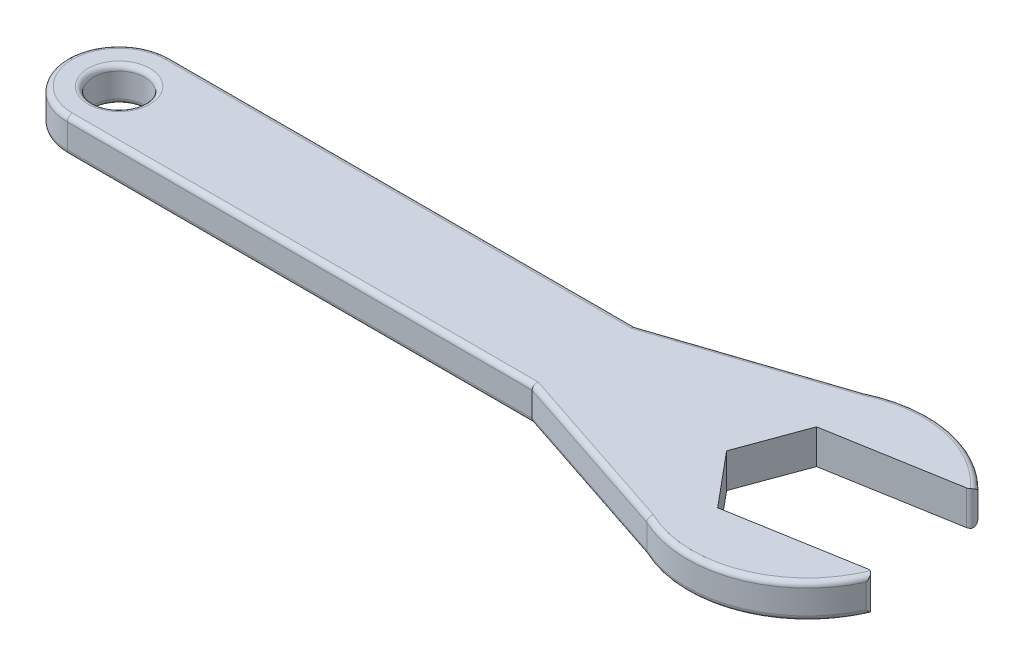
SolidWorks part; units mm, degrees
ref_plane "Alzado" through (0, 0, 0) normal (0, 0, 1) x (1, 0, 0)
ref_plane "Planta" through (0, 0, 0) normal (0, 1, 0) x (1, 0, 0)
ref_plane "Vista lateral" through (0, 0, 0) normal (1, 0, 0) x (0, 0, -1)
sketch "Croquis1" plane through (0, 0, 0) normal (0, 1, 0) x (1, 0, 0)
  line L0 (150, 30) -> (249.7385, 63.1208)
  line L1 (-150, -30) -> (150, -30)
  line L2 (-150, -30) -> (-150, 30)
  line L3 (-150, 30) -> (150, 30)
  line L7 (150, -30) -> (249.7385, -63.1208)
  arc A0 (249.7385, -63.1208) -> (249.7385, 63.1208) centre (280, 0) ccw
  point P0 (0, 0)
  dimension "D1" = 280
extrude "Saliente-Extruir1" add sketch "Croquis1" along normal blind 20
sketch "Croquis3" plane through (0, 0, 0) normal (0, 1, 0) x (1, 0, 0)
  line L2 (294.0332, 38.1904) -> (253.9427, 31.2483)
  line L3 (253.9427, 31.2483) -> (239.9095, -6.9421)
  line L4 (239.9095, -6.9421) -> (265.9668, -38.1904)
  line L5 (265.9668, -38.1904) -> (306.0573, -31.2483)
  line L7 (294.0332, 38.1904) -> (368.8825, 51.1514)
  line L8 (306.0573, -31.2483) -> (380.9066, -18.2873)
  line L9 (368.8825, 51.1514) -> (380.9066, -18.2873)
  line L11 (306.0573, -31.2483) -> (313.0739, -12.1531) [skipped]
  line L12 (307.0618, 22.5663) -> (294.0332, 38.1904) [skipped]
extrude "Cortar-Extruir1" cut sketch "Croquis3" along normal blind 32
fillet "Redondeo1" radius 30 2 edges at (-150, 10, 30) (-150, 10, -30)
sketch "Croquis5" plane through (0, 0, 0) normal (0, 1, 0) x (1, 0, 0)
  circle A0 centre (-119.916, 0) radius 15
extrude "Cortar-Extruir2" cut sketch "Croquis5" along normal blind 31
sketch "Croquis6" plane through (0, 0, 0) normal (0, 1, 0) x (1, 0, 0)
  line L0 (-78.8524, 0) -> (137.996, 0) construction
  line L1 (-78.8524, 15.1218) -> (137.996, 15.1218)
  line L2 (-78.8524, -15.1218) -> (137.996, -15.1218)
  arc A0 (-78.8524, 15.1218) -> (-78.8524, -15.1218) centre (-78.8524, 0) ccw
  arc A1 (137.996, -15.1218) -> (137.996, 15.1218) centre (137.996, 0) ccw
  point P3 (29.5718, 0)
extrude "Cortar-Extruir3" cut sketch "Croquis6" along normal blind 7
sketch "Croquis8" plane through (0, 0, 0) normal (0, 1, 0) x (1, 0, 0)
  line L0 (-93.9742, 0) -> (153.1178, 0) construction
  arc A0 (-78.8524, 15.1218) -> (-78.8524, -15.1218) centre (-78.8524, 0) ccw construction
  arc A1 (137.996, -15.1218) -> (137.996, 15.1218) centre (137.996, 0) ccw construction
  text T0 "Ingenieria fotonica " font "Century Gothic" height 3.5
extrude "Saliente-Extruir2" add sketch "Croquis8" along normal blind 7
fillet "Redondeo2" radius 3 24 edges at (29.5718, 0, -15.1218) (153.1178, 0, 0) (29.5718, 0, 15.1218) (15, 20, 30) (-141.2132, 20, 21.2132) (-141.2132, 20, -21.2132) (15, 0, -30) (-141.2132, 0, -21.2132) (-141.2132, 0, 21.2132) (333.5859, 10, -45.0394) (345.61, 10, 24.3993) (-119.916, 20, 15) (-119.916, 0, 15) (-93.9742, 0, 0) (306.2148, 20, 64.906) (199.8692, 20, 46.5604) (294.7561, 20, -68.427) (199.8692, 20, -46.5604) (15, 20, -30) (306.2148, 0, 64.906) (294.7561, 0, -68.427) (199.8692, 0, -46.5604) (199.8692, 0, 46.5604) (15, 0, 30)
